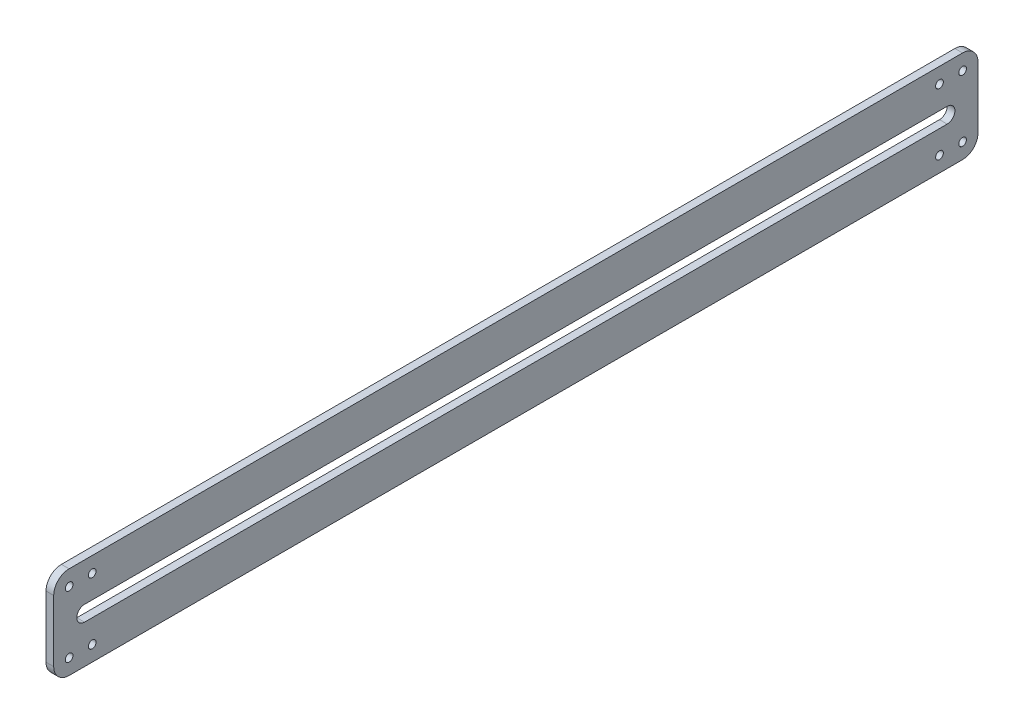
SolidWorks part; units mm, degrees
ref_plane "Front Plane" through (0, 0, 0) normal (0, 0, 1) x (1, 0, 0)
ref_plane "Top Plane" through (0, 0, 0) normal (0, 1, 0) x (1, 0, 0)
ref_plane "Right Plane" through (0, 0, 0) normal (1, 0, 0) x (0, 0, -1)
sketch "Sketch1" plane through (0, 0, 0) normal (1, 0, 0) x (0, 0, -1)
  line L1 (-184.15, -19.05) -> (184.15, -19.05)
  line L2 (-190.5, -12.7) -> (-190.5, 12.7)
  line L3 (-184.15, 19.05) -> (184.15, 19.05)
  line L4 (190.5, -12.7) -> (190.5, 12.7)
  line L5 (-190.5, -19.05) -> (190.5, 19.05) construction
  line L6 (-190.5, 19.05) -> (190.5, -19.05) construction
  arc A0 (184.15, 19.05) -> (190.5, 12.7) centre (184.15, 12.7) cw
  arc A1 (190.5, -12.7) -> (184.15, -19.05) centre (184.15, -12.7) cw
  arc A2 (-184.15, -19.05) -> (-190.5, -12.7) centre (-184.15, -12.7) cw
  arc A3 (-190.5, 12.7) -> (-184.15, 19.05) centre (-184.15, 12.7) cw
  point P0 (0, 0)
  dimension "D3" = 6.35
  dimension "D1" = 381
  dimension "D2" = 38.1
extrude "Outer Cut" add sketch "Sketch1" along normal mid plane 3.175
sketch "Sketch2" plane through (1.5875, 0, 0) normal (1, 0, 0) x (0, 0, -1)
  line L0 (-190.5, 0) -> (190.5, 0) construction
  line L1 (-190.5, 12.7) -> (-190.5, -12.7) construction
  line L2 (190.5, -12.7) -> (190.5, 12.7) construction
  line L3 (-177.8, 0) -> (177.8, 0) construction
  line L4 (-177.8, 3.175) -> (177.8, 3.175)
  line L5 (-177.8, -3.175) -> (177.8, -3.175)
  arc A0 (-177.8, 3.175) -> (-177.8, -3.175) centre (-177.8, 0) ccw
  arc A1 (177.8, -3.175) -> (177.8, 3.175) centre (177.8, 0) ccw
  point P2 (0, 0)
  dimension "D1" = 6.35
  dimension "D3" = 12.7
  dimension "D4" = 12.7
extrude "Slots" cut sketch "Sketch2" against normal through all
sketch "Sketch3" plane through (1.5875, 0, 0) normal (1, 0, 0) x (0, 0, -1)
  line L0 (-190.5, 12.7) -> (-190.5, -12.7) construction
  line L1 (184.15, 19.05) -> (-184.15, 19.05) construction
  line L2 (0, 0) -> (0, 19.05) construction
  line L3 (0, 0) -> (-190.5, 0) construction
  circle A0 centre (-184.15, 12.7) radius 1.5875
  circle A1 centre (-174.625, 12.7) radius 1.5875
  circle A2 centre (-174.625, -12.7) radius 1.5875
  circle A3 centre (-184.15, -12.7) radius 1.5875
  circle A4 centre (174.625, 12.7) radius 1.5875
  circle A5 centre (184.15, 12.7) radius 1.5875
  circle A6 centre (184.15, -12.7) radius 1.5875
  circle A7 centre (174.625, -12.7) radius 1.5875
  dimension "D1" = 3.175
  dimension "D2" = 6.35
  dimension "D3" = 6.35
  dimension "D5" = 9.525
  dimension "D4" = 2
extrude "Mount Holes" cut sketch "Sketch3" against normal through all
